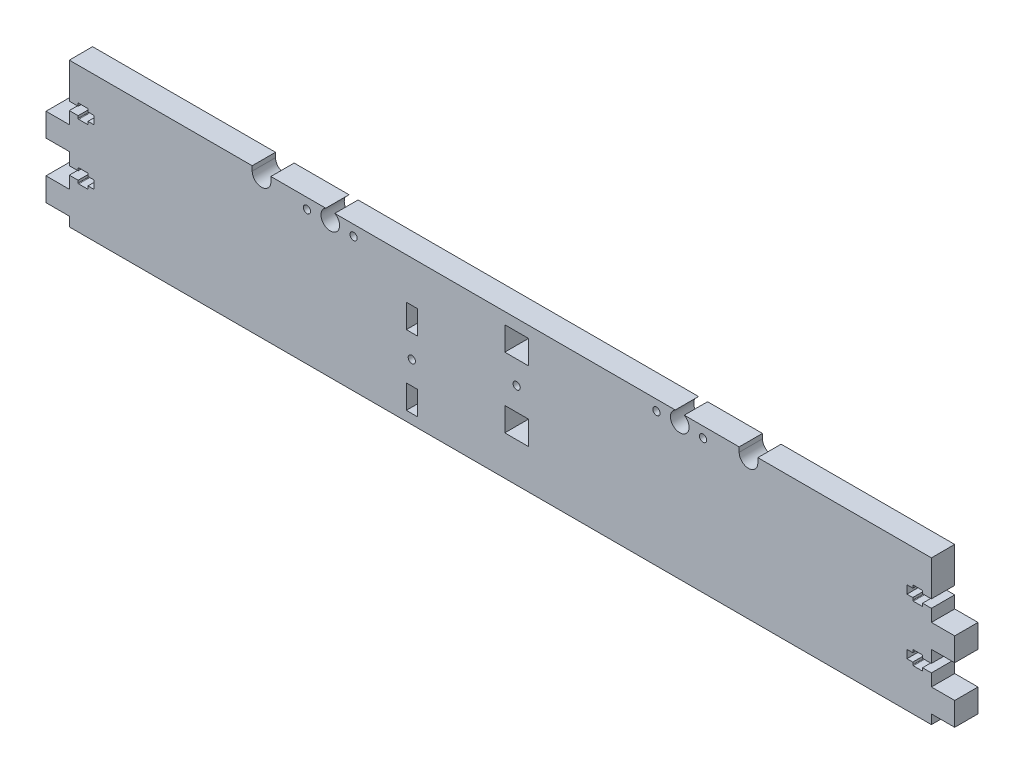
SolidWorks part; units mm, degrees
ref_plane "Front Plane" through (0, 0, 0) normal (0, 0, 1) x (1, 0, 0)
ref_plane "Top Plane" through (0, 0, 0) normal (0, 1, 0) x (1, 0, 0)
ref_plane "Right Plane" through (0, 0, 0) normal (1, 0, 0) x (0, 0, -1)
sketch "Sketch1" plane through (0, 0, 0) normal (0, 0, 1) x (1, 0, 0)
  line L0 (0, 0) -> (-185, 0)
  line L1 (-185, 0) -> (-185, -62) construction
  line L2 (0, -62) -> (-185, -62)
  line L3 (-185, -62) -> (-185, -58)
  line L4 (-185, -58) -> (-195, -58)
  line L5 (-195, -58) -> (-195, -48)
  line L6 (-195, -48) -> (-185, -48)
  line L7 (-185, -48) -> (-185, -34)
  line L8 (-185, -34) -> (-195, -34)
  line L9 (-195, -34) -> (-195, -24)
  line L10 (-195, -24) -> (-185, -24)
  line L11 (0, -62) -> (0, 0)
  line L12 (-185, -24) -> (-185, 0)
  line L13 (-195, -58) -> (-195, -24) construction
  line L14 (-195, -29) -> (-185, -29) construction
  line L15 (-195, -53) -> (-185, -53) construction
  dimension "D1" = 185
  dimension "D2" = 10
  dimension "D3" = 10
  dimension "D4" = 10
  dimension "D5" = 24
  dimension "D6" = 29
  dimension "D7" = 62
extrude "MainBody" add sketch "Sketch1" along normal blind 10
sketch "Sketch3" plane through (0, 0, 10) normal (0, 0, 1) x (1, 0, 0)
  line L0 (-185, -17) -> (-174.5, -17) construction
  line L1 (-185, 0) -> (-185, -24) construction
  line L2 (-185, -18.75) -> (-181.2, -18.75)
  line L3 (-181.2, -18.75) -> (-181.2, -19.75)
  line L4 (-180.95, -20) -> (-177.25, -20)
  line L5 (-177, -19.75) -> (-177, -18.75)
  line L6 (-177, -18.75) -> (-174.5, -18.75)
  line L7 (-174.5, -18.75) -> (-174.5, -15.25)
  line L8 (-181.2, -18.75) -> (-177, -18.75) construction
  line L9 (-195, -24) -> (-195, -34) construction
  line L10 (-181.2, -15.25) -> (-177, -15.25) construction
  line L11 (-177, -15.25) -> (-174.5, -15.25)
  line L12 (-177, -14.25) -> (-177, -15.25)
  line L13 (-180.95, -14) -> (-177.25, -14)
  line L14 (-181.2, -15.25) -> (-181.2, -14.25)
  line L15 (-185, -15.25) -> (-181.2, -15.25)
  line L16 (-185, -18.75) -> (-185, -15.25)
  line L17 (-185, -24) -> (-185, -34) construction
  line L19 (-195, -24) -> (-195, -34) construction
  line L20 (-195, -29) -> (-185, -29) construction
  line L21 (-181.2, -42.75) -> (-177, -42.75) construction
  line L22 (-181.2, -39.25) -> (-177, -39.25) construction
  line L23 (-185, -41) -> (-174.5, -41) construction
  line L24 (-185, -39.25) -> (-185, -42.75)
  line L25 (-185, -42.75) -> (-181.2, -42.75)
  line L26 (-181.2, -42.75) -> (-181.2, -43.75)
  line L27 (-180.95, -44) -> (-177.25, -44)
  line L28 (-177, -43.75) -> (-177, -42.75)
  line L29 (-177, -42.75) -> (-174.5, -42.75)
  line L30 (-174.5, -39.25) -> (-174.5, -42.75)
  line L31 (-177, -39.25) -> (-174.5, -39.25)
  line L32 (-177, -38.25) -> (-177, -39.25)
  line L33 (-180.95, -38) -> (-177.25, -38)
  line L34 (-181.2, -39.25) -> (-181.2, -38.25)
  line L35 (-185, -39.25) -> (-181.2, -39.25)
  line L36 (-181.2, -15.25) -> (-177, -15.25) construction
  arc A0 (-177.25, -20) -> (-177, -19.75) centre (-177.25, -19.75) ccw
  arc A1 (-181.2, -19.75) -> (-180.95, -20) centre (-180.95, -19.75) ccw
  arc A2 (-181.2, -14.25) -> (-180.95, -14) centre (-180.95, -14.25) cw
  arc A3 (-177.25, -14) -> (-177, -14.25) centre (-177.25, -14.25) cw
  arc A4 (-177.25, -44) -> (-177, -43.75) centre (-177.25, -43.75) ccw
  arc A5 (-181.2, -43.75) -> (-180.95, -44) centre (-180.95, -43.75) ccw
  arc A6 (-181.2, -38.25) -> (-180.95, -38) centre (-180.95, -38.25) cw
  arc A7 (-177.25, -38) -> (-177, -38.25) centre (-177.25, -38.25) cw
  point P6 (-195, -29)
  point P15 (-177, -20)
  point P18 (-181.2, -20)
  point P29 (-181.2, -14)
  point P30 (-177, -14)
  point P62 (-177, -44)
  point P63 (-181.2, -44)
  point P64 (-181.2, -38)
  point P65 (-177, -38)
  dimension "D2" = 8
  dimension "D7" = 0.25
  dimension "D1" = 10.5
  dimension "D3" = 1.75
  dimension "D4" = 3
  dimension "D5" = 12
  dimension "D6" = 4.2
extrude "ScrewCutouts" cut sketch "Sketch3" against normal through all
mirror "Mirror1" about plane through (0, 0, 0) normal (1, 0, 0) of "ScrewCutouts", "MainBody"
sketch "Sketch2" plane through (0, 0, 10) normal (0, 0, 1) x (1, 0, 0)
  line L0 (0, 0) -> (0, -62) construction
  line L1 (-185, -62) -> (185, -62) construction
  line L2 (2, 0) -> (2, -62) construction
  line L3 (185, 0) -> (-185, 0) construction
  line L4 (-63, -4.5) -> (-83, -4.5) construction
  line L5 (-73, -7.5) -> (-73, 0.5) construction
  line L6 (77, -7.5) -> (77, 0.5) construction
  line L7 (67, -4.5) -> (87, -4.5) construction
  circle A0 centre (-73, -3.5) radius 4
  circle A1 centre (-83, -4.5) radius 1.55
  circle A2 centre (-63, -4.5) radius 1.55
  circle A3 centre (67, -4.5) radius 1.55
  circle A4 centre (87, -4.5) radius 1.55
  circle A5 centre (77, -3.5) radius 4
  dimension "D1" = 3.1
  dimension "D2" = 8
  dimension "D4" = 3.5
  dimension "D5" = 75
  dimension "D6" = 2
  dimension "D3" = 10
  dimension "D7" = 1
extrude "RodCutouts" cut sketch "Sketch2" against normal through all
sketch "Sketch4" plane through (0, 0, 10) normal (0, 0, 1) x (1, 0, 0)
  line L0 (77, -3.5) -> (-73, -3.5) construction
  line L1 (2, -3.5) -> (2, -62) construction
  line L2 (-185, -62) -> (185, -62) construction
  line L3 (7, -45.1) -> (7, -4.9) construction
  line L4 (75.0635, 0) -> (-71.0635, 0) construction
  line L5 (7, -10) -> (7, -40) construction
  line L6 (1.9, -4.9) -> (12.1, -4.9)
  line L7 (1.9, -4.9) -> (1.9, -15.1)
  line L8 (1.9, -15.1) -> (12.1, -15.1)
  line L9 (12.1, -4.9) -> (12.1, -15.1)
  line L10 (1.9, -4.9) -> (12.1, -15.1) construction
  line L11 (1.9, -15.1) -> (12.1, -4.9) construction
  line L12 (1.9, -34.9) -> (12.1, -34.9)
  line L13 (1.9, -34.9) -> (1.9, -45.1)
  line L14 (1.9, -45.1) -> (12.1, -45.1)
  line L15 (12.1, -34.9) -> (12.1, -45.1)
  line L16 (1.9, -34.9) -> (12.1, -45.1) construction
  line L17 (1.9, -45.1) -> (12.1, -34.9) construction
  circle A0 centre (7, -25) radius 1.55
  point P12 (7, -10)
  point P17 (7, -40)
  dimension "D8" = 3.1
  dimension "D1" = 10.2
  dimension "D2" = 10.2
  dimension "D3" = 10.2
  dimension "D4" = 10.2
  dimension "D5" = 30
  dimension "D6" = 10
  dimension "D7" = 5
extrude "Cut-Extrude3" cut sketch "Sketch4" against normal through all
sketch "Sketch5" plane through (0, 0, 10) normal (0, 0, 1) x (1, 0, 0)
  line L0 (-38, 0) -> (-38, -62) construction
  line L1 (-74.9365, 0) -> (-185, 0) construction
  line L2 (-185, -62) -> (185, -62) construction
  line L3 (-40.35, -27.85) -> (-40.35, -47.65) construction
  line L4 (-40.35, -17.65) -> (-35.65, -17.65)
  line L5 (-40.35, -17.65) -> (-40.35, -27.85)
  line L6 (-40.35, -27.85) -> (-35.65, -27.85)
  line L7 (-35.65, -17.65) -> (-35.65, -27.85)
  line L8 (-40.35, -17.65) -> (-35.65, -27.85) construction
  line L9 (-40.35, -27.85) -> (-35.65, -17.65) construction
  line L10 (-40.35, -47.65) -> (-35.65, -47.65)
  line L11 (-40.35, -47.65) -> (-40.35, -57.85)
  line L12 (-40.35, -57.85) -> (-35.65, -57.85)
  line L13 (-35.65, -47.65) -> (-35.65, -57.85)
  line L14 (-40.35, -47.65) -> (-35.65, -57.85) construction
  line L15 (-40.35, -57.85) -> (-35.65, -47.65) construction
  line L16 (-35.65, -47.65) -> (-35.65, -27.85) construction
  line L17 (-40.35, -37.75) -> (-35.65, -37.75) construction
  line L18 (-73, -3.5) -> (77, -3.5) construction
  line L19 (2, -3.5) -> (2, -62) construction
  line L20 (2, -32.75) -> (-195, -32.75) construction
  line L21 (-195, -24) -> (-195, -34) construction
  line L22 (-31.45, 8.9944) -> (-31.45, 5) construction
  line L23 (75.0635, 0) -> (-71.0635, 0) construction
  line L24 (-28.25, 8.9944) -> (-28.25, 5)
  line L25 (-34.65, 8.9944) -> (-34.65, 5)
  circle A0 centre (-38, -37.75) radius 1.55
  arc A1 (-28.25, 8.9944) -> (-34.65, 8.9944) centre (-31.45, 8.9944) ccw
  arc A2 (-34.65, 5) -> (-28.25, 5) centre (-31.45, 5) ccw
  point P6 (-38, -22.75)
  point P11 (-38, -52.75)
  point P34 (-31.45, 6.9972)
  dimension "D3" = 10.2
  dimension "D4" = 10.2
  dimension "D5" = 30
  dimension "D6" = 3.1
  dimension "D9" = 3.2
  dimension "D1" = 4.7
  dimension "D2" = 0
  dimension "D7" = 40
  dimension "D8" = 5
  dimension "D10" = 5
  dimension "D11" = 1
extrude "EndstopHolder" cut sketch "Sketch5" against normal through all
sketch "Sketch6" plane through (0, 0, 10) normal (0, 0, 1) x (1, 0, 0)
  line L0 (-40.35, -47.65) -> (-40.35, -27.85) construction
  line L1 (-42.35, -47.65) -> (-27.65, -47.65) construction
  line L3 (-27.65, -53.65) -> (-27.65, -41.65) construction
  line L4 (-29.65, -53.65) -> (-29.65, -41.65)
  line L5 (-25.65, -53.65) -> (-25.65, -41.65)
  line L6 (-35.65, -47.65) -> (-40.35, -47.65) construction
  line L7 (-35.65, -57.85) -> (-35.65, -47.65) construction
  arc A0 (-29.65, -53.65) -> (-25.65, -53.65) centre (-27.65, -53.65) ccw
  arc A1 (-25.65, -41.65) -> (-29.65, -41.65) centre (-27.65, -41.65) ccw
  point P10 (-27.65, -47.65)
  dimension "D1" = 2
  dimension "D2" = 12
  dimension "D3" = 8
  dimension "D4" = 0
extrude "EndstopWires" [suppressed] cut sketch "Sketch6" against normal through all
sketch "Sketch7" plane through (0, 0, 10) normal (0, 0, 1) x (1, 0, 0)
  line L0 (-73, -3.5) -> (77, -3.5) construction
  line L1 (2, -3.5) -> (2, -62) construction
  line L3 (-102.5, 0) -> (-102.5, -2) construction
  line L4 (-74.9365, 0) -> (-185, 0) construction
  line L5 (-98.5, 0) -> (-98.5, -2)
  line L6 (-106.5, 0) -> (-106.5, -2)
  line L7 (106.5, 0) -> (106.5, -2) construction
  line L8 (102.5, 0) -> (102.5, -2)
  line L9 (110.5, 0) -> (110.5, -2)
  line L10 (-185, -62) -> (185, -62) construction
  arc A0 (-98.5, 0) -> (-106.5, 0) centre (-102.5, 0) ccw
  arc A1 (-106.5, -2) -> (-98.5, -2) centre (-102.5, -2) ccw
  arc A2 (102.5, 0) -> (110.5, 0) centre (106.5, 0) cw
  arc A3 (110.5, -2) -> (102.5, -2) centre (106.5, -2) cw
  point P12 (-102.5, -1)
  point P19 (106.5, -1)
  dimension "D3" = 4
  dimension "D1" = 2
  dimension "D2" = 104.5
extrude "Cut-Extrude4" cut sketch "Sketch7" against normal through all
equation "\"Y-ROD-SPACING\"=75"
equation "\"D5@Sketch2\"=\"Y-ROD-SPACING\""
equation "\"Y-BED-OFFSET\"=2"
equation "\"D6@Sketch2\"=\"Y-BED-OFFSET\""
equation "\"T-SLOT-NUT-FILLET-RADIUS\"=0.25"
equation "\"D7@Sketch3\"=\"T-SLOT-NUT-FILLET-RADIUS\""
equation "\"T-SLOT-SCREW-SHAFT-RADIUS\"=1.75"
equation "\"D3@Sketch3\"=\"T-SLOT-SCREW-SHAFT-RADIUS\""
equation "\"T-SLOT-SCREW-SHAFT-CUTOUT-LENGTH\"=10.5"
equation "\"D1@Sketch3\"=\"T-SLOT-SCREW-SHAFT-CUTOUT-LENGTH\""
equation "\"T-SLOT-NUT-DEPTH\"=4.2"
equation "\"D6@Sketch3\"=\"T-SLOT-NUT-DEPTH\""
equation "\"T-SLOT-NUT-WIDTH\"=3"
equation "\"D4@Sketch3\"=\"T-SLOT-NUT-WIDTH\""
equation "\"T-SLOT-NUT-END-DISTANCE\"=8"
equation "\"D2@Sketch3\"=\"T-SLOT-NUT-END-DISTANCE\""
equation "\"ACRYLIC-TAB-CUTOUT-SIZE\"=\"ACRYLIC-THICKNESS\"+\"ACRYLIC-TAB-TOLERANCE\"*2"
equation "\"D1@Sketch4\"=\"ACRYLIC-TAB-CUTOUT-SIZE\""
equation "\"D2@Sketch4\"=\"ACRYLIC-TAB-CUTOUT-SIZE\""
equation "\"D3@Sketch4\"=\"ACRYLIC-TAB-CUTOUT-SIZE\""
equation "\"D4@Sketch4\"=\"ACRYLIC-TAB-CUTOUT-SIZE\""
equation "\"ACRYLIC-M3-HOLE\"=3.1"
equation "\"D8@Sketch4\"=\"ACRYLIC-M3-HOLE\""
equation "\"Y-BED-ROD-INSET\"=3.5"
equation "\"D1@Sketch2\"=\"ACRYLIC-M3-HOLE\""
equation "\"D4@Sketch2\"=\"Y-BED-ROD-INSET\""
equation "\"SMOOTHROD-CAP-SCREW-DISTANCE\"=20"
equation "\"D3@Sketch2\"=\"SMOOTHROD-CAP-SCREW-DISTANCE\"/2"
equation "\"ACRYLIC-TAB-WIDTH\"=\"ACRYLIC-THICKNESS\""
equation "\"FRAME-WIDTH-INNER\"=370"
equation "\"D2@Sketch1\"=\"ACRYLIC-TAB-WIDTH\""
equation "\"D3@Sketch1\"=\"ACRYLIC-TAB-WIDTH\""
equation "\"D4@Sketch1\"=\"ACRYLIC-TAB-WIDTH\""
equation "\"D1@Sketch1\"=\"FRAME-WIDTH-INNER\"/2"
equation "\"X-ROD-SPACING\"=45"
equation "\"Z-ROD-SPACING\"=17.5"
equation "\"ACRYLIC-THICKNESS\"=10"
equation "\"ACRYLIC-THICKNESS2\"=4.5"
equation "\"NEMA17-HOLE-SPACING\"=31"
equation "\"NEMA17-CENTRAL-CUTOUT\"=22.5"
equation "\"Z-BRACKET-REACH\"=55"
equation "\"TOP-BRACKET-SPACING\"=40"
equation "\"SMOOTHROD-X-LENGTH\"=350"
equation "\"SMOOTHROD-Y-LENGTH\"=350"
equation "\"SMOOTHROD-Z-LENGTH\"=350"
equation "\"SMOOTHROD-TIGHTENING-HEADROOM\"=.25"
equation "\"LEADSCREW-Z-LENGTH\"=300"
equation "\"SCREW-LENGTH-FRAME\"=\"ACRYLIC-THICKNESS\" + 10"
equation "\"SCREW-HEAD-RADIUS\"=6"
equation "\"PRINTED-X-SMOOTHROD-DIAMETER\"=8.2"
equation "\"PRINTED-X-SMOOTHROD-CUTOUT\"=10"
equation "\"PRINTED-X-BASE-HEIGHT\"=10"
equation "\"PRINTED-LM8UU-CUTOUT-SIZE\"=15.25"
equation "\"PRINTED-LM8UU-CUTOUT-LENGTH\"=24.5"
equation "\"PRINTED-X-IDLER-HEIGHT\"=16"
equation "\"PSU-MOUNTING-WIDTH\"=95"
equation "\"PSU-MOUNTING-HEIGHT\"=177"
equation "\"D1@MainBody\"=\"ACRYLIC-THICKNESS\""
equation "\"D1@Sketch5\"=\"ACRYLIC-THICKNESS2\"+\"ACRYLIC-TAB-TOLERANCE\"*2"
equation "\"D3@Sketch5\"=\"ACRYLIC-TAB-CUTOUT-SIZE\""
equation "\"D4@Sketch5\"=\"ACRYLIC-TAB-CUTOUT-SIZE\""
equation "\"D6@Sketch5\"=\"ACRYLIC-M3-HOLE\""
equation "\"Y-BED-SCREW-SPACING\"=209"
equation "\"Y-BED-SCREW-CUTOUT-SLOT-HEIGHT\"=2"
equation "\"Z-ROD-INSET\"=16"
equation "\"Y-BELT-TO-ROD-DISTANCE\"=20"
equation "\"SPOOL-HOLDER-ROD-SPACING\"=150"
equation "\"D1@Sketch7\"=\"Y-BED-SCREW-CUTOUT-SLOT-HEIGHT\""
equation "\"D2@Sketch7\"=\"Y-BED-SCREW-SPACING\"/2"
equation "\"ACRYLIC-TAB-TOLERANCE\"=.1"
equation "\"SCREW-LENGTH-MOTOR\"=\"ACRYLIC-THICKNESS\" + 5"
equation "\"SCREW-LENGTH-EXTRUDER\"=28"
equation "\"ACRYLIC-X-CARRIAGE-WIDTH\"=55"
equation "\"ACRYLIC-X-CARRIAGE-HEIGHT\"=75"
equation "\"ACRYLIC-X-CARRIAGE-LM8UU-CUTOUT-WIDTH\"=24.25"
equation "\"ACRYLIC-X-CARRIAGE-SCREW-SPACING-X\"=15"
equation "\"ACRYLIC-X-CARRIAGE-SCREW-SPACING-Y\"=33"
equation "\"ACRYLIC-X-CARRIAGE-CENTER-TAB-SPACING\"=14"
equation "\"ACRYLIC-X-CARRIAGE-EXTRUDER-OFFSET\"=26"
equation "\"ACRYLIC-X-CARRIAGE-EXTRUDER-ANGLE\"=90"
equation "\"ACRYLIC-X-CARRIAGE-EXTRUDER-SHELF-DEPTH\"=\"ACRYLIC-X-CARRIAGE-EXTRUDER-OFFSET\" + 28"
equation "\"ACRYLIC-X-CARRIAGE-EXTRUDER-BRACE-SPACING\"=23"
equation "\"ACRYLIC-X-CARRIAGE-EXTRUDER-BRACE-TAB-OFFSET\"=20"
equation "\"ACRYLIC-X-CARRIAGE-EXTRUDER-BRACE-HEIGHT\"=35"
equation "\"ACRYLIC-X-CARRIAGE-EXTRUDER-BRACE-SCREW-SPACING\"=22"
equation "\"PRINTED-M3-HOLE\"=3.5"
equation "\"ACRYLIC-X-CARRIAGE-LM8UU-CUTOUT-HEIGHT\"=11.5"
equation "\"ACRYLIC-X-CARRIAGE-DUAL-WIDTH-MULTIPLIER\"=1.65"
equation "\"ACRYLIC-X-CARRIAGE-DUAL-HOTEND-SPACING\"=42"
equation "\"ACRYLIC-X-CARRIAGE-DUAL-WIDTH\"=103"
equation "\"ACRYLIC-X-CARRIAGE-DUAL-HOTEND-SEPARATION\"=35"
equation "\"ACRYLIC-X-CARRIAGE-DUAL-MOUNT-PLATE-DEPTH\"=76"
equation "\"ACRYLIC-X-CARRIAGE-DUAL-MOUNT-BRACE-WIDTH\"=45"
equation "\"ACRYLIC-X-CARRIAGE-DUAL-MOUNT-SCREW-WIDTH\"=40"
equation "\"BLOWER-FAN-WIDTH\"=15"
